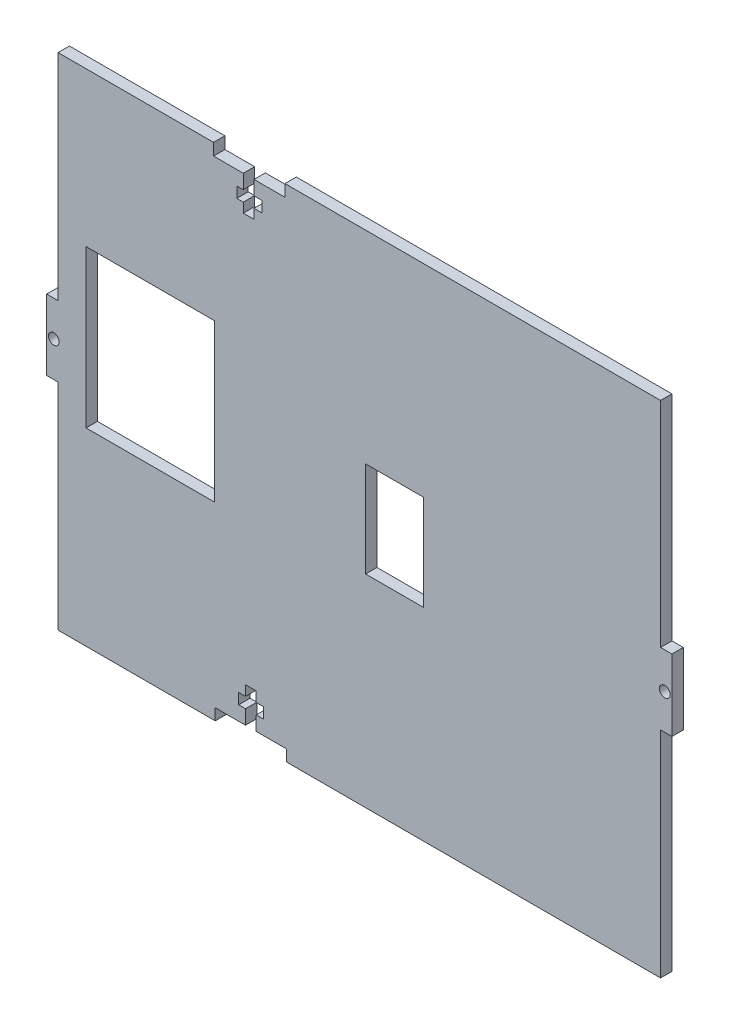
SolidWorks part; units mm, degrees
ref_plane "Front Plane" through (0, 0, 0) normal (0, 0, 1) x (1, 0, 0)
ref_plane "Top Plane" through (0, 0, 0) normal (0, 1, 0) x (1, 0, 0)
ref_plane "Right Plane" through (0, 0, 0) normal (1, 0, 0) x (0, 0, -1)
sketch "Sketch1" plane through (0, 0, 0) normal (0, 0, 1) x (1, 0, 0)
  line L1 (-87.5, 70) -> (87.5, 70)
  line L2 (-87.5, 70) -> (-87.5, -70)
  line L3 (-87.5, -70) -> (87.5, -70)
  line L4 (87.5, 70) -> (87.5, -70)
  line L5 (-87.5, 70) -> (87.5, -70) construction
  line L6 (-87.5, -70) -> (87.5, 70) construction
  point P0 (0, 0)
  dimension "D1" = 140
  dimension "D2" = 175
extrude "Boss-Extrude1" add sketch "Sketch1" along normal blind 3.18
sketch "Sketch2" plane through (0, 0, 3.18) normal (0, 0, 1) x (1, 0, 0)
  line L0 (-87.5, -70) -> (87.5, -70) construction
  line L5 (87.5, 0) -> (-87.9045, 0) construction
  line L6 (87.5, -70) -> (87.5, 70) construction
  line L12 (87.5, -70) -> (87.5, 70) construction
  line L38 (-87.5, 70) -> (-87.5, -70) construction
  line L39 (-87.5, 70) -> (-84.32, 70)
  line L40 (-87.5, 70) -> (-87.5, 9.875)
  line L41 (-87.5, 9.875) -> (-84.32, 9.875)
  line L42 (-84.32, 70) -> (-84.32, 9.875)
  line L43 (-87.5, -70) -> (-84.32, -70)
  line L44 (-87.5, -70) -> (-87.5, -9.875)
  line L45 (-87.5, -9.875) -> (-84.32, -9.875)
  line L46 (-84.32, -70) -> (-84.32, -9.875)
  line L47 (87.5, -9.875) -> (84.32, -9.875)
  line L48 (84.32, -73.9291) -> (84.32, -9.875)
  line L49 (87.5, -73.9291) -> (84.32, -73.9291)
  line L50 (87.5, -73.9291) -> (87.5, -9.875)
  line L51 (87.5, 10.125) -> (84.32, 10.125)
  line L52 (84.32, 75.125) -> (84.32, 10.125)
  line L53 (87.5, 75.125) -> (84.32, 75.125)
  line L54 (87.5, 75.125) -> (87.5, 10.125)
  line L70 (-28.8549, -66.82) -> (-20.3341, -66.82)
  line L71 (-40.3341, -70) -> (-20.3341, -70)
  line L72 (-40.3341, -70) -> (-40.3341, -66.82)
  line L73 (-40.3341, -66.82) -> (-31.8549, -66.82)
  line L74 (-20.3341, -70) -> (-20.3341, -66.82)
  line L75 (-31.8549, -62.82) -> (-33.773, -62.82)
  line L76 (-87.5, -70) -> (87.5, -70) construction
  line L77 (-31.8549, -57) -> (-28.8549, -57)
  line L78 (-31.8549, -57) -> (-31.8549, -59.82)
  line L80 (-28.8549, -57) -> (-28.8549, -59.82)
  line L83 (-26.773, -62.82) -> (-28.8549, -62.82)
  line L84 (-26.773, -62.82) -> (-26.773, -59.82)
  line L85 (-26.773, -59.82) -> (-28.8549, -59.82)
  line L86 (-33.773, -62.82) -> (-33.773, -59.82)
  line L91 (-31.8549, -59.82) -> (-33.773, -59.82)
  line L98 (-31.8549, -62.82) -> (-31.8549, -66.82)
  line L99 (-28.8549, -62.82) -> (-28.8549, -66.82)
  circle A0 centre (-85.5, 0) radius 1.5
  circle A1 centre (85.5, 0) radius 1.5
  point P6 (0, 0)
  point P7 (0, 0)
  point P67 (-32.11, -66.8097)
  point P72 (-32.3859, -61.3492)
  point P77 (-32.3859, -59.7197)
  dimension "D11" = 3
  dimension "D12" = 2
  dimension "D3" = 3
  dimension "D2" = 19.75
  dimension "D4" = 20
  dimension "D5" = 65
  dimension "D9" = 3.18
  dimension "D10" = 3.18
  dimension "D13" = 20
  dimension "D14" = 7
  dimension "D15" = 3.18
  dimension "D16" = 3
  dimension "D17" = 3
  dimension "D18" = 4
  dimension "D19" = 13
extrude "Cut-Extrude1" cut sketch "Sketch2" against normal through all
sketch "Sketch11" plane through (0, 0, 0) normal (0, 0, -1) x (-1, 0, 0)
  line L0 (-84.32, 70) -> (84.32, 70) construction
  line L1 (20.7931, 66.67) -> (29.4791, 66.67)
  line L2 (20.7931, 66.67) -> (20.7931, 70)
  line L3 (20.7931, 70) -> (40.7931, 70)
  line L4 (40.7931, 66.67) -> (40.7931, 70)
  line L6 (30.7931, 0) -> (0, 0) construction
  line L7 (29.4791, 62.67) -> (29.4791, 66.67)
  line L8 (29.4791, 57) -> (32.4791, 57)
  line L9 (29.4791, 57) -> (29.4791, 59.67)
  line L11 (32.4791, 57) -> (32.4791, 59.67)
  line L12 (32.4791, 66.67) -> (40.7931, 66.67)
  line L14 (27.2931, 59.67) -> (29.4791, 59.67)
  line L15 (27.2931, 59.67) -> (27.2931, 62.67)
  line L16 (27.2931, 62.67) -> (29.4791, 62.67)
  line L17 (34.2931, 59.67) -> (34.2931, 62.67)
  line L22 (30.7931, 57) -> (30.7931, 0) construction
  line L25 (32.4791, 62.67) -> (32.4791, 66.67)
  line L26 (32.4791, 59.67) -> (34.2931, 59.67)
  line L28 (32.4791, 62.67) -> (34.2931, 62.67)
  point P8 (30.4223, 62.891)
  point P11 (30.7931, 70)
  point P15 (30.4223, 62.1751)
  dimension "D1" = 20
  dimension "D2" = 3
  dimension "D3" = 3
  dimension "D4" = 13
  dimension "D5" = 7
  dimension "D6" = 4
sketch "Sketch12" plane through (0, 0, 0) normal (0, 0, -1) x (-1, 0, 0)
  line L1 (40.471, -17.0656) -> (76.4831, -17.0656)
  line L2 (40.471, -17.0656) -> (40.471, 26.8946)
  line L3 (40.471, 26.8946) -> (76.4831, 26.8946)
  line L4 (76.4831, -17.0656) -> (76.4831, 26.8946)
  line L5 (40.471, -17.0656) -> (76.4831, 26.8946) construction
  line L6 (40.471, 26.8946) -> (76.4831, -17.0656) construction
  point P0 (58.477, 4.9145)
extrude "Cut-Extrude6" cut sketch "Sketch12" against normal through all
sketch "Sketch13" plane through (0, 0, 0) normal (0, 0, -1) x (-1, 0, 0)
  line L1 (-17.9359, -13.3526) -> (-1.7618, -13.3526)
  line L2 (-17.9359, -13.3526) -> (-17.9359, 13.3526)
  line L3 (-17.9359, 13.3526) -> (-1.7618, 13.3526)
  line L4 (-1.7618, -13.3526) -> (-1.7618, 13.3526)
  line L5 (-17.9359, -13.3526) -> (-1.7618, 13.3526) construction
  line L6 (-17.9359, 13.3526) -> (-1.7618, -13.3526) construction
  point P0 (-9.8488, 0)
extrude "Cut-Extrude7" cut sketch "Sketch13" against normal through all
extrude "Cut-Extrude11" cut sketch "Sketch11" against normal blind 10
equation "\"sheet\"= 3.18mm"
equation "\"screwD\"= 2.94mm"
equation "\"tabW\"= 20mm"
equation "\"nut2\"= 6.5mm"
